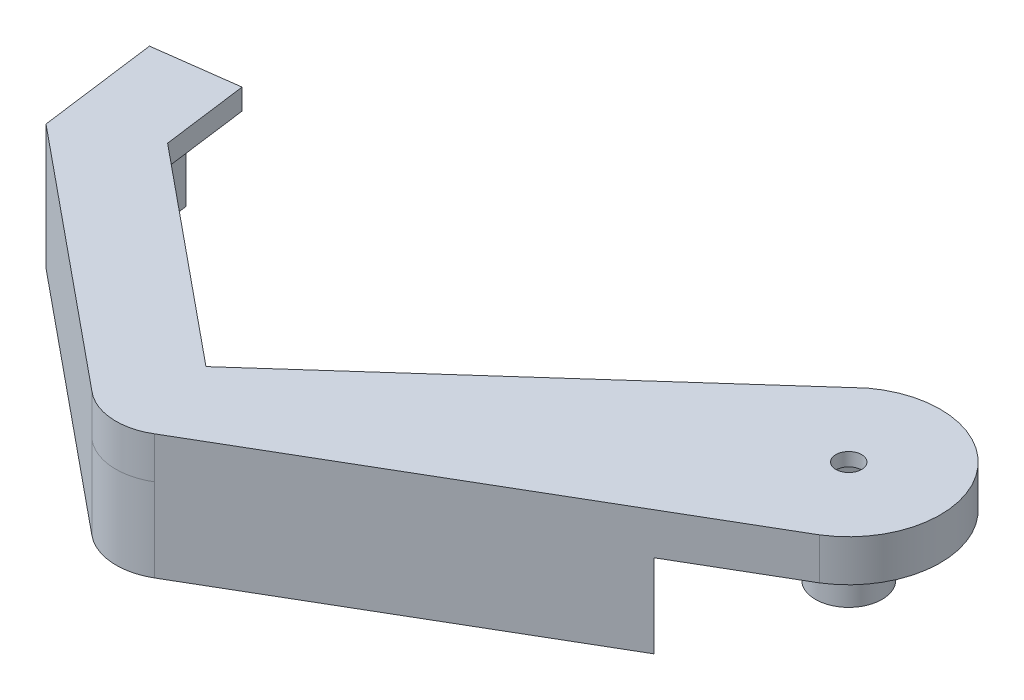
SolidWorks part; units mm, degrees
ref_plane "Front Plane" through (0, 0, 0) normal (0, 0, 1) x (1, 0, 0)
ref_plane "Top Plane" through (0, 0, 0) normal (0, 1, 0) x (1, 0, 0)
ref_plane "Right Plane" through (0, 0, 0) normal (1, 0, 0) x (0, 0, -1)
sketch "Sketch1" plane through (0, 0, 0) normal (0, 1, 0) x (1, 0, 0)
  circle A0 centre (0, 0) radius 10.3349
  dimension "D1" = 20.6698
extrude "Boss-Extrude1" add sketch "Sketch1" along normal blind 4
sketch "Sketch2" plane through (0, 0, 0) normal (0, -1, 0) x (1, 0, 0)
  circle A0 centre (0, 0) radius 4
other "Move Face1" flip direction yes face at (0, 0, 10.3349) offset 3 parameters "D1"=3
sketch "Sketch5" plane through (0, 3, 0) normal (0, -1, 0) x (1, 0, 0)
  line L0 (0, 0) -> (-48.7465, 34.9826) construction
  line L1 (-48.7465, 34.9826) -> (-78.7465, 10.3971) construction
  line L2 (0, 0) -> (-78.7465, 10.3971) construction
  line L3 (-78.7465, 10.3971) -> (-80.7177, -4.5326) construction
  line L5 (-75.4582, -2.5675) -> (-74.0969, 7.743)
  line L6 (-74.0969, 7.743) -> (-48.5447, 28.6834)
  line L12 (-6.5426, -8.8428) -> (-48.5447, 28.6834)
  line L13 (-52.8156, 38.1124) -> (-83.396, 13.0512)
  line L15 (-75.4582, -2.5675) -> (-85.2869, -1.2698)
  line L16 (-85.2869, -1.2698) -> (-83.396, 13.0512)
  line L17 (-44.6294, 38.7624) -> (5.2508, 9.6659)
  arc A1 (-52.8156, 38.1124) -> (-44.6294, 38.7624) centre (-48.2723, 32.7672) cw
  arc A3 (5.2508, 9.6659) -> (-6.5426, -8.8428) centre (0, 0) cw
  point P9 (-80.7177, -4.5326)
  point P15 (0, 0)
  dimension "D1" = 10.4
  dimension "D2" = 60
  dimension "D3" = 30
  dimension "D4" = 105
  dimension "D7" = 5
  dimension "D12" = 33.0367
extrude "Boss-Extrude3" add sketch "Sketch5" along normal blind 5
sketch "Sketch6" plane through (0, -2, 0) normal (0, -1, 0) x (1, 0, 0)
  circle A0 centre (0, 0) radius 6.3
  dimension "D1" = 12.6
extrude "Boss-Extrude4" add sketch "Sketch6" along normal blind 0.3
other "Move Face2" flip direction yes face at (0, 4, 10.3349) offset 1 parameters "D1"=1
sketch "Sketch8" plane through (0, -2, 0) normal (0, -1, 0) x (1, 0, 0)
  line L0 (-85.2869, -1.2698) -> (-81.4016, -1.7828)
  line L1 (-85.2869, -1.2698) -> (-75.4582, -2.5675) construction
  line L2 (-81.4016, -1.7828) -> (-79.6672, 11.3539)
  line L3 (-79.6672, 11.3539) -> (-48.9483, 36.5285)
  line L9 (-83.396, 13.0512) -> (-85.2869, -1.2698)
  line L10 (-12.814, 12.5754) -> (-48.9483, 36.5285)
  line L11 (-52.8156, 38.1124) -> (-83.396, 13.0512)
  line L12 (-44.6294, 38.7624) -> (-6.72, 16.6488)
  line L13 (-52.8156, 38.1124) -> (-83.396, 13.0512) construction
  arc A0 (-6.72, 16.6488) -> (-12.814, 12.5754) centre (0, 0) ccw
  arc A1 (-44.6294, 38.7624) -> (-52.8156, 38.1124) centre (-48.2574, 32.5794) ccw
  arc A2 (-44.6294, 38.7624) -> (-52.8156, 38.1124) centre (-48.2723, 32.7672) ccw construction
  point P10 (-52.8156, 38.1124)
  point P21 (0, 0)
extrude "Boss-Extrude5" add sketch "Sketch8" along normal blind 10
sketch "Sketch9" plane through (0, -2, 0) normal (0, -1, 0) x (1, 0, 0)
  line L0 (-48.5447, 28.6834) -> (-6.5426, -8.8428) construction
  line L1 (-17.906, 1.3097) -> (-75.4582, -2.5675)
  line L2 (-75.4582, -2.5675) -> (-81.4016, -1.7828)
  line L3 (-81.4016, -1.7828) -> (-79.6672, 11.3539)
  line L4 (-81.4016, -1.7828) -> (-79.6672, 11.3539) construction
  line L5 (-79.6672, 11.3539) -> (-48.9483, 36.5285)
  line L6 (-48.9483, 36.5285) -> (-12.814, 12.5754)
  arc A0 (-12.814, 12.5754) -> (-17.906, 1.3097) centre (0, 0) ccw
extrude "Cut-Extrude3" cut sketch "Sketch9" against normal blind 2.5
ref_axis "Axis2" through (0, -2, 0) along (0, 1, 0)
ref_plane "Plane1" through (0, 0, 0) normal (-0.5525, 0, -0.8335) x (-0.8335, 0, 0.5525)
sketch "Sketch10" plane through (0, 0, 0) normal (-0.5525, 0, -0.8335) x (-0.8335, 0, 0.5525)
  line L0 (17.9538, -2) -> (17.9538, 0.5) construction
  line L1 (17.9538, 1.01) -> (20.9538, 1.01)
  line L2 (17.9538, -1.99) -> (17.9538, 1.01)
  arc A0 (20.9538, 1.01) -> (17.9538, -1.99) centre (17.9538, 1.01) cw
  dimension "D1" = 3
revolve "Revolve3" add sketch "Sketch10" angle 360 about axis through (0, -2, 0) along (0, 1, 0) reverse direction yes
sketch "Sketch11" plane through (-7.2977, 0, -8.1681) normal (-0.6663, 0, -0.7457) x (-0.7457, 0, 0.6663)
  line L0 (-18.7151, -2) -> (-18.7151, 3)
  line L1 (55.3114, 3) -> (-1.0126, 3) construction
  line L2 (-18.7151, 3) -> (19.8414, 3)
  line L3 (19.8414, 3) -> (19.8414, -2)
  line L4 (19.8414, -2) -> (-18.7151, -2)
extrude "Cut-Extrude4" cut sketch "Sketch11" along normal blind 22
sketch "Sketch13" plane through (0, -2.3, 0) normal (0, -1, 0) x (1, 0, 0)
  circle A2 centre (0, 0) radius 4
  dimension "D1" = 8
extrude "Boss-Extrude6" add sketch "Sketch13" along normal blind 7
sketch "Sketch14" plane through (0, -9.3, 0) normal (0, -1, 0) x (1, 0, 0)
  circle A0 centre (0, 0) radius 1.55
  dimension "D1" = 3.1
extrude "Cut-Extrude6" cut sketch "Sketch14" against normal blind 14.3
ref_plane "Plane2" through (0, -1.1, 0) normal (0, -1, 0) x (-1, 0, 0)
sketch "Sketch15" plane through (0, -1.1, 0) normal (0, -1, 0) x (-1, 0, 0)
  line L1 (2.0704, -2.7773) -> (3.4404, 0.4043)
  line L2 (3.4404, 0.4043) -> (1.37, 3.1817)
  line L3 (1.37, 3.1817) -> (-2.0704, 2.7773)
  line L4 (-2.0704, 2.7773) -> (-3.4404, -0.4043)
  line L5 (-3.4404, -0.4043) -> (-1.37, -3.1817)
  line L6 (-1.37, -3.1817) -> (2.0704, -2.7773)
  circle A0 centre (0, 0) radius 3 construction
extrude "Cut-Extrude7" cut sketch "Sketch15" against normal blind 2.5
sketch "Sketch17" plane through (5.54, 0, 9.4972) normal (0.5039, 0, 0.8638) x (0.8638, 0, -0.5039)
  line L2 (-19.4143, -8.2622) -> (11.2348, -8.2622)
  line L3 (-19.4143, -8.2622) -> (-19.4143, 7.3647)
  line L4 (-19.4143, 7.3647) -> (11.2348, 7.3647)
  line L5 (11.2348, -8.2622) -> (11.2348, 7.3647)
revolve "Cut-Revolve1" cut sketch "Sketch17" angle 270 about L5
